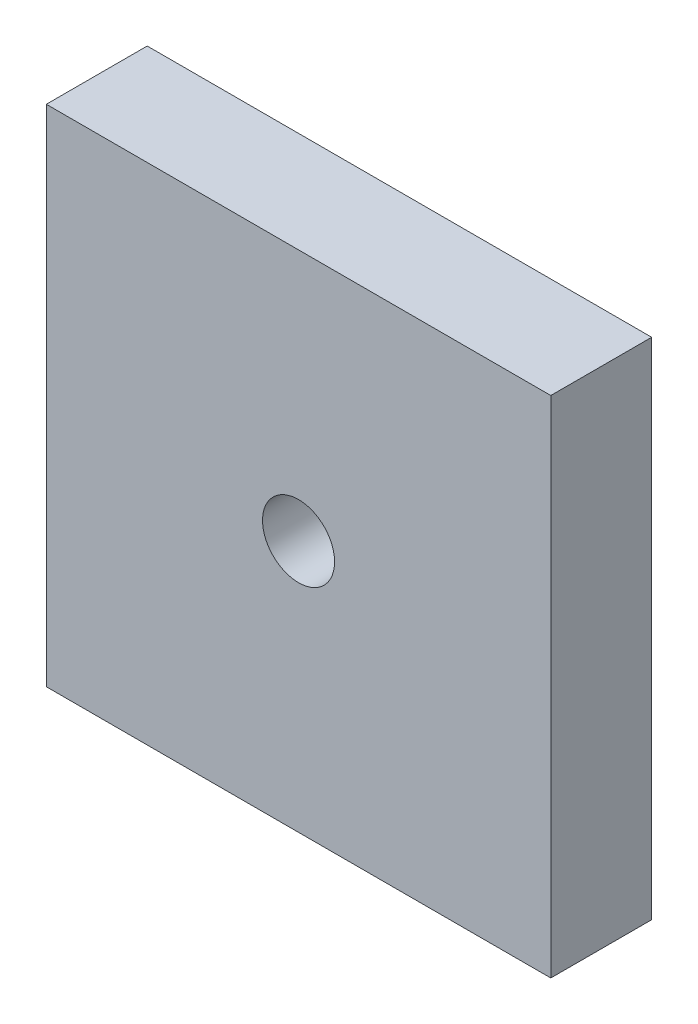
SolidWorks part; units mm, degrees
ref_plane "前视基准面" through (0, 0, 0) normal (0, 0, 1) x (1, 0, 0)
ref_plane "上视基准面" through (0, 0, 0) normal (0, 1, 0) x (1, 0, 0)
ref_plane "右视基准面" through (0, 0, 0) normal (1, 0, 0) x (0, 0, -1)
sketch "草图1" plane through (0, 0, 0) normal (0, 0, 1) x (1, 0, 0)
  line L1 (-7, 7) -> (7, 7)
  line L2 (-7, 7) -> (-7, -7)
  line L3 (-7, -7) -> (7, -7)
  line L4 (7, 7) -> (7, -7)
  line L5 (-7, 7) -> (7, -7) construction
  line L6 (-7, -7) -> (7, 7) construction
  circle A0 centre (0, 0) radius 1
  point P0 (0, 0)
extrude "凸台-拉伸1" add sketch "草图1" along normal blind 2.8 contours L2 L1 L4 L3
extrude "切除-拉伸1" cut sketch "草图1<3>" along normal blind 2.8 contours A0
sketch "草图1<3>" plane through (0, 0, 0) normal (0, 0, 1) x (1, 0, 0) same geometry as "草图1"
